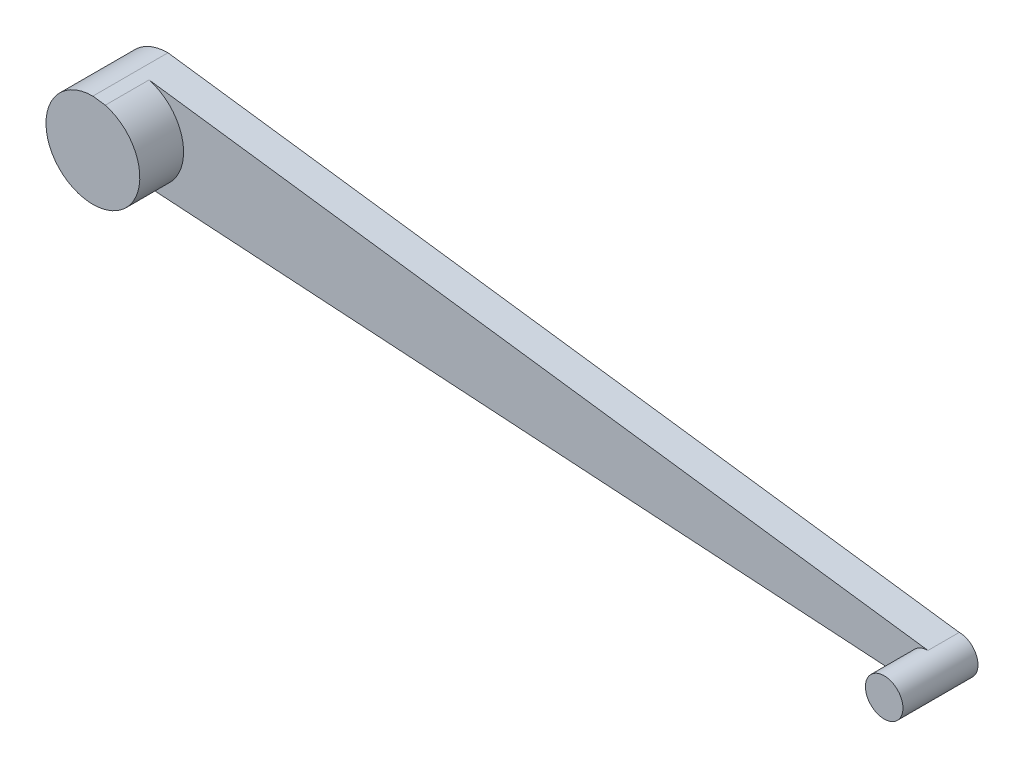
SolidWorks part; units mm, degrees
ref_plane "Alzado" through (0, 0, 0) normal (0, 0, 1) x (1, 0, 0)
ref_plane "Planta" through (0, 0, 0) normal (0, 1, 0) x (1, 0, 0)
ref_plane "Vista lateral" through (0, 0, 0) normal (1, 0, 0) x (0, 0, -1)
sketch "Croquis1" plane through (0, 0, 0) normal (0, 0, 1) x (1, 0, 0)
  line L0 (0, 0) -> (-25.3, 0) construction
  line L1 (-25.3, 0) -> (-25.3, 2.5) construction
  line L2 (-25.3, 2.5) -> (0, 0) construction
  line L3 (-25.3, 4) -> (0, 0.6)
  line L4 (-25.3, 1) -> (0, -0.6)
  circle A0 centre (0, 0) radius 0.6
  circle A1 centre (-25.3, 2.5) radius 1.5
  dimension "D3" = 3
  dimension "D4" = 1.2
  dimension "D1" = 25.3
  dimension "D2" = 2.5
extrude "Saliente-Extruir1" add sketch "Croquis1" along normal blind 2.4 contours L3 A1 | A0 L4 region at (-25.3001, 2.4993, 0) region at (0, 0, 0)
extrude "Saliente-Extruir2" add sketch "Croquis1<3>" along normal blind 1 contours A1 L4 A0 L3 region at (-13.886, 1.368, 0)
sketch "Croquis1<3>" plane through (0, 0, 0) normal (0, 0, 1) x (1, 0, 0) same geometry as "Croquis1"
